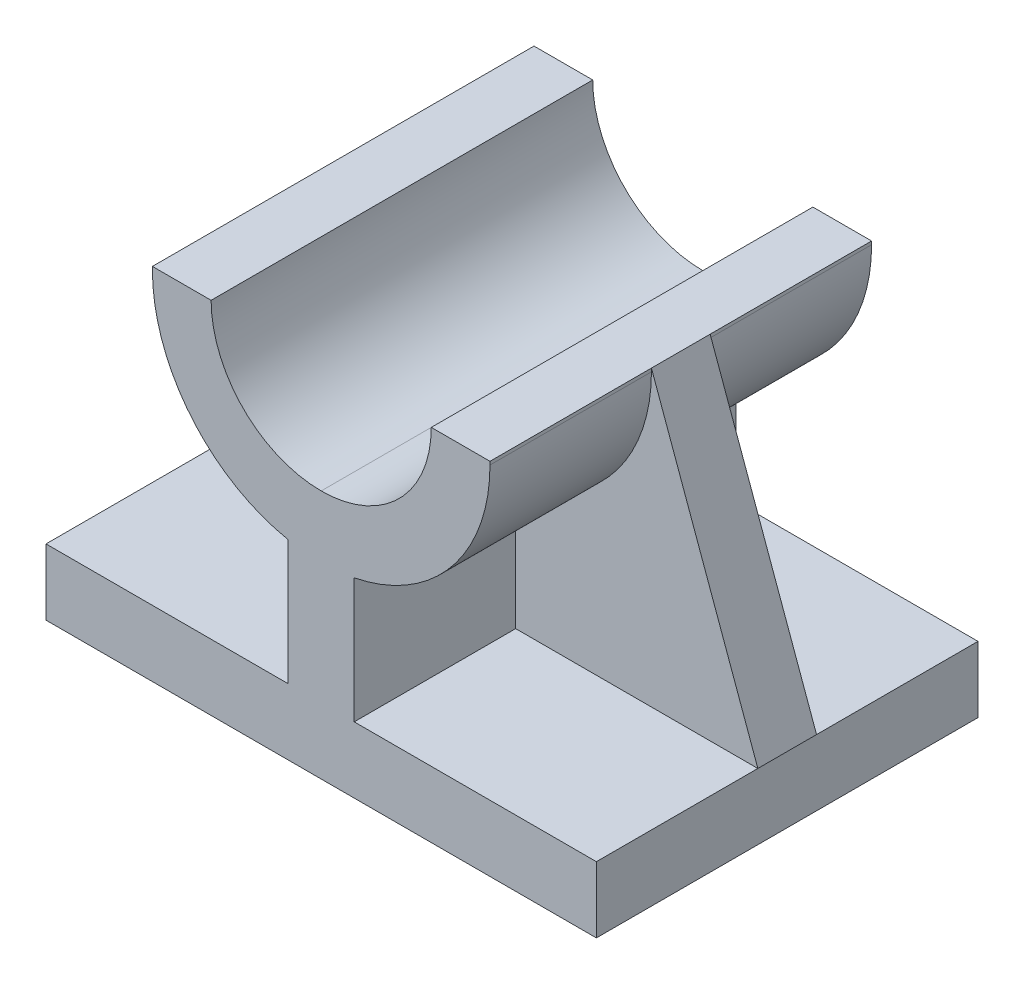
SolidWorks part; units mm, degrees
ref_plane "Front Plane" through (0, 0, 0) normal (0, 0, 1) x (1, 0, 0)
ref_plane "Top Plane" through (0, 0, 0) normal (0, 1, 0) x (1, 0, 0)
ref_plane "Right Plane" through (0, 0, 0) normal (1, 0, 0) x (0, 0, -1)
sketch "Sketch1" plane through (0, 0, 0) normal (0, 1, 0) x (1, 0, 0)
  line L1 (0, 0) -> (190.5, 0)
  line L2 (0, 0) -> (0, -132.08)
  line L3 (0, -132.08) -> (190.5, -132.08)
  line L4 (190.5, 0) -> (190.5, -132.08)
  dimension "D1" = 190.5
  dimension "D2" = 132.08
extrude "Boss-Extrude1" add sketch "Sketch1" along normal blind 22.86
sketch "Sketch2" plane through (0, 22.86, 0) normal (0, 1, 0) x (1, 0, 0)
  line L0 (0, -66.04) -> (190.5, -66.04) construction
  line L1 (0, 0) -> (0, -132.08) construction
  line L2 (190.5, -132.08) -> (190.5, 0) construction
  line L3 (95.25, 0) -> (95.25, -132.08) construction
  line L4 (190.5, 0) -> (0, 0) construction
  line L5 (0, -132.08) -> (190.5, -132.08) construction
  line L7 (36.83, -132.08) -> (153.67, -132.08)
  line L8 (36.83, -132.08) -> (36.83, 0)
  line L9 (36.83, 0) -> (153.67, 0)
  line L10 (153.67, -132.08) -> (153.67, 0)
  line L11 (36.83, -132.08) -> (153.67, 0) construction
  line L12 (36.83, 0) -> (153.67, -132.08) construction
  point P12 (95.25, -66.04)
  dimension "D1" = 116.84
extrude "Boss-Extrude2" add sketch "Sketch2" along normal blind 101.6
sketch "Sketch3" plane through (153.67, 0, 0) normal (1, 0, 0) x (0, 0, -1)
  line L0 (-132.08, 73.66) -> (0, 73.66) construction
  line L1 (-132.08, 124.46) -> (-132.08, 22.86) construction
  line L2 (0, 124.46) -> (0, 22.86) construction
  line L3 (-132.08, 124.46) -> (0, 124.46) construction
  line L4 (-76.2, 22.86) -> (-55.88, 22.86)
  line L5 (-76.2, 22.86) -> (-76.2, 124.46)
  line L6 (-76.2, 124.46) -> (-55.88, 124.46)
  line L7 (-55.88, 22.86) -> (-55.88, 124.46)
  line L8 (-76.2, 22.86) -> (-55.88, 124.46) construction
  line L9 (-76.2, 124.46) -> (-55.88, 22.86) construction
  point P6 (-66.04, 73.66)
  dimension "D1" = 20.32
extrude "Boss-Extrude3" add sketch "Sketch3" along normal blind 36.83
sketch "Sketch4" plane through (153.67, 0, 0) normal (1, 0, 0) x (0, 0, -1)
  line L0 (-132.08, 124.46) -> (-132.08, 22.86) construction
  line L1 (-76.2, 22.86) -> (-132.08, 22.86)
  line L2 (-76.2, 22.86) -> (-76.2, 66.04)
  line L3 (-76.2, 66.04) -> (-132.08, 66.04)
  line L4 (-132.08, 22.86) -> (-132.08, 66.04)
  dimension "D1" = 43.18
sketch "Sketch5" plane through (153.67, 0, 0) normal (1, 0, 0) x (0, 0, -1)
  line L0 (0, 124.46) -> (0, 22.86) construction
  line L1 (-55.88, 22.86) -> (0, 22.86)
  line L2 (-55.88, 22.86) -> (-55.88, 66.04)
  line L3 (-55.88, 66.04) -> (0, 66.04)
  line L4 (0, 22.86) -> (0, 66.04)
  dimension "D1" = 43.18
extrude "Cut-Extrude1" cut sketch "Sketch5" against normal blind 46.99
extrude "Cut-Extrude2" cut sketch "Sketch4" against normal blind 46.99
sketch "Sketch6" plane through (36.83, 0, 0) normal (-1, 0, 0) x (0, 0, 1)
  line L0 (132.08, 124.46) -> (132.08, 22.86) construction
  line L1 (0, 22.86) -> (132.08, 22.86)
  line L2 (0, 22.86) -> (0, 66.04)
  line L3 (0, 66.04) -> (132.08, 66.04)
  line L4 (132.08, 22.86) -> (132.08, 66.04)
  dimension "D1" = 43.18
extrude "Cut-Extrude3" cut sketch "Sketch6" against normal blind 46.99
sketch "Sketch10" plane through (0, 124.46, 0) normal (0, 1, 0) x (1, 0, 0)
  line L0 (95.25, 0) -> (95.25, -132.08) construction
  line L1 (153.67, 0) -> (36.83, 0) construction
  line L2 (36.83, -132.08) -> (153.67, -132.08) construction
  line L4 (57.15, -132.08) -> (133.35, -132.08)
  line L5 (57.15, -132.08) -> (57.15, 0)
  line L6 (57.15, 0) -> (133.35, 0)
  line L7 (133.35, -132.08) -> (133.35, 0)
  line L8 (57.15, -132.08) -> (133.35, 0) construction
  line L9 (57.15, 0) -> (133.35, -132.08) construction
  point P6 (95.25, -66.04)
  point P11 (133.35, -66.04)
  dimension "D1" = 76.2
extrude "Cut-Extrude4" cut sketch "Sketch10" against normal blind 38.1
chamfer "Chamfer1" distance 36.83 distance2 101.6 1 edges at (190.5, 124.46, 66.04) first distance on face at (157.7975, 124.46, 66.04)
fillet "Fillet1" radius 58.42 3 edges at (36.83, 66.04, 66.04) (153.67, 66.04, 27.94) (153.67, 66.04, 104.14)
fillet "Fillet2" radius 38.1 2 edges at (133.35, 86.36, 66.04) (57.15, 86.36, 66.04)
